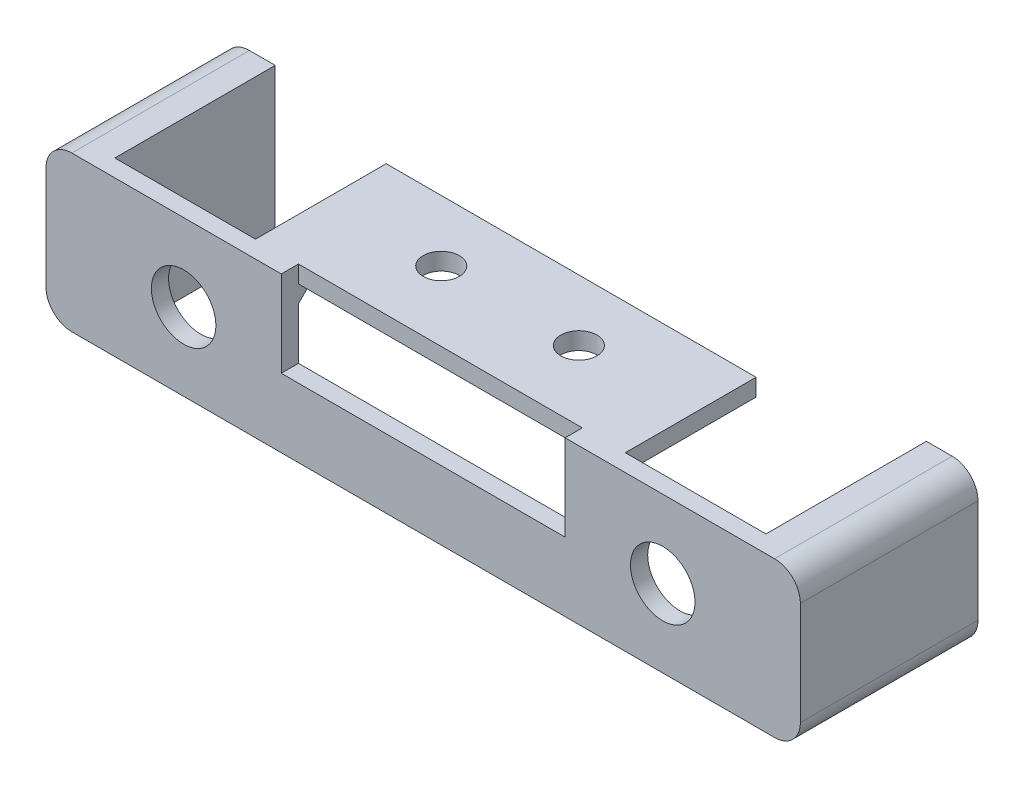
SolidWorks part; units mm, degrees
ref_plane "Front Plane" through (0, 0, 0) normal (0, 0, 1) x (1, 0, 0)
ref_plane "Top Plane" through (0, 0, 0) normal (0, 1, 0) x (1, 0, 0)
ref_plane "Right Plane" through (0, 0, 0) normal (1, 0, 0) x (0, 0, -1)
sketch "Sketch1" plane through (0, 0, 0) normal (0, 0, 1) x (1, 0, 0)
  line L0 (0, -1000) -> (0, 49000) construction
  line L1 (-43.85, -18) -> (43.85, -18)
  line L2 (-43.85, -18) -> (-43.85, 0)
  line L3 (-43.85, 0) -> (43.85, 0) construction
  line L4 (43.85, -18) -> (43.85, 0)
  line L5 (-43.85, -9) -> (43.85, -9) construction
  line L6 (-43.85, 0) -> (-16.5, 0)
  line L11 (-16.5, 0) -> (-16.5, -10)
  line L12 (-16.5, -10) -> (16.5, -10)
  line L13 (16.5, -10) -> (16.5, 0)
  line L14 (16.5, 0) -> (43.85, 0)
  line L15 (-37.85, -24) -> (-37.85, 0) construction
  circle A0 centre (-27.85, -9) radius 3.75
  circle A2 centre (27.85, -9) radius 3.75
  point P4 (0, 0)
  point P14 (0, -10)
  dimension "D3" = 7.5
  dimension "D4" = 10
  dimension "D1" = 18
  dimension "D2" = 6
  dimension "D5" = 33
  dimension "D6" = 10
extrude "Boss-Extrude1" add sketch "Sketch1" along normal blind 2
sketch "Sketch3" plane through (0, 0, 0) normal (0, 1, 0) x (1, 0, 0)
  line L0 (-16.5, 0) -> (-43.85, 0) construction
  line L1 (-21.5, 0) -> (21.5, 0)
  line L2 (-21.5, 0) -> (-21.5, 15.2)
  line L3 (-21.5, 15.2) -> (21.5, 15.2)
  line L4 (21.5, 0) -> (21.5, 15.2)
  line L5 (-8, 8.1) -> (8, 8.1) construction
  line L6 (-16.5, -2) -> (-16.5, 0) construction
  circle A0 centre (-8, 8.1) radius 2.1
  circle A1 centre (8, 8.1) radius 2.1
  point P6 (0, 0)
  point P12 (0, 8.1)
  dimension "D2" = 4.2
  dimension "D1" = 16
  dimension "D3" = 5
  dimension "D4" = 6
  dimension "D5" = 5
extrude "Boss-Extrude2" add sketch "Sketch3" against normal blind 2
sketch "Sketch4" plane through (-21.5, 0, 0) normal (-1, 0, 0) x (0, 0, 1)
  line L0 (-2, -2) -> (0, -4)
  line L1 (-15.2, -2) -> (0, -2) construction
  line L2 (0, 0) -> (0, -18) construction
  line L3 (0, -4) -> (0, -2)
  line L4 (0, -2) -> (-2, -2)
  dimension "D1" = 2
extrude "Boss-Extrude3" add sketch "Sketch4" against normal blind 5
sketch "Sketch5" plane through (0, 0, 0) normal (0, 0, -1) x (-1, 0, 0)
  line L0 (43.85, -18) -> (-43.85, -18) construction
  line L1 (43.85, 0) -> (37.85, 0)
  line L2 (43.85, 0) -> (43.85, -18)
  line L3 (43.85, -18) -> (37.85, -18)
  line L4 (37.85, 0) -> (37.85, -18)
  line L5 (37.85, -24) -> (37.85, 0) construction
extrude "Boss-Extrude4" add sketch "Sketch5" along normal up to surface (18.65 mm away) up to face at (0, 0, -1.8667)
mirror "Mirror2" about plane through (0, 0, 0) normal (1, 0, 0) of "Boss-Extrude4", "Boss-Extrude3"
fillet "Fillet1" radius 3 4 edges at (43.85, -18, -8.325) (43.85, 0, -8.325) (-43.85, -18, -8.325) (-43.85, 0, -8.325)
equation "\"width\"= 24"
equation "\"thk\"= 3"
equation "\"holesize\"= 4.2"
equation "\"holedistance\"= ( 20 + 12 ) / 2"
equation "\"threaded_hole\"= 3.9"
equation "\"fillet_radius\"= 2"
equation "\"ground_clearance\"= 25"
equation "\"tire_thk\"= 3"
equation "\"innerwheel_diam\" = \"wheel_diam\"-2*\"tire_thk\""
equation "\"innerwheel_thk\"= 8"
equation "\"wheel_diam\"= 2*(\"width\"/2+\"ground_clearance\")"
equation "\"coloursensor_holesize\"= 2.65"
equation "\"hole_to_edge\" = 4"
equation "\"D1@Sketch3\"=\"holedistance\""
equation "\"D2@Sketch3\"=\"holesize\""
